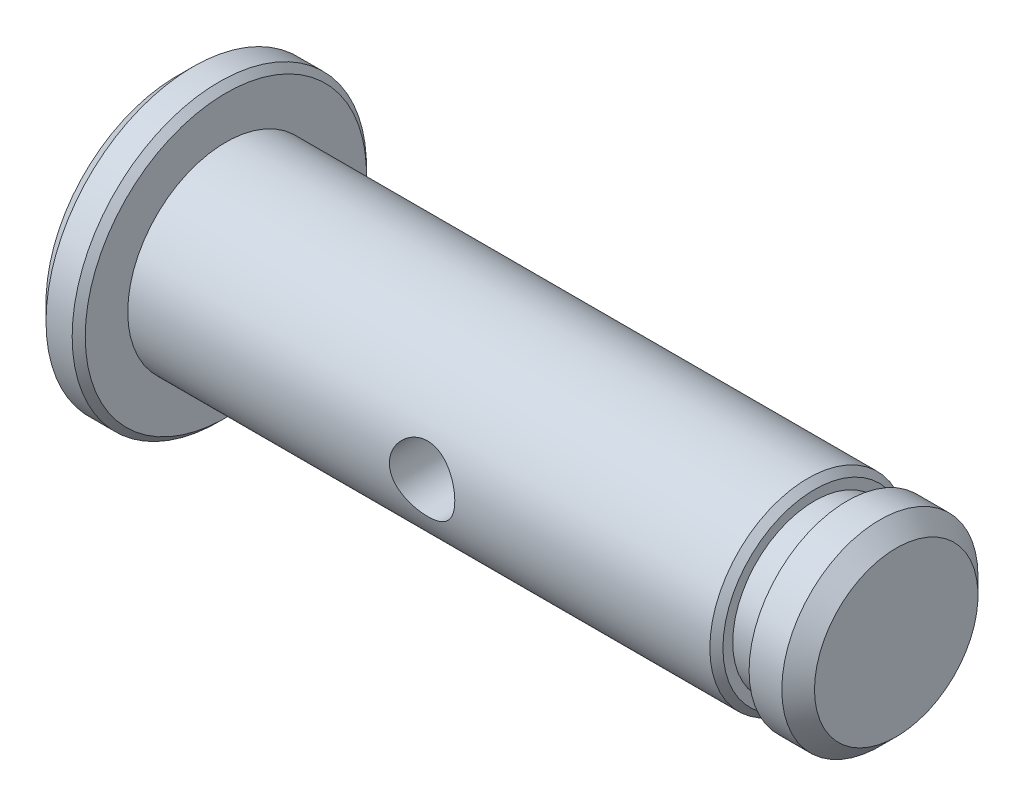
SolidWorks part; units mm, degrees
material "6061-T6 (GB)"
ref_plane "前视" through (0, 0, 0) normal (0, 0, 1) x (1, 0, 0)
ref_plane "上视" through (0, 0, 0) normal (0, 1, 0) x (1, 0, 0)
ref_plane "右视" through (0, 0, 0) normal (1, 0, 0) x (0, 0, -1)
sketch "草图1" plane through (0, 0, 0) normal (0, 0, 1) x (1, 0, 0)
  line L0 (0, 0) -> (77.1831, 0) construction
  line L1 (0, 0) -> (0, 4.5)
  line L2 (0, 4.5) -> (1.5, 4.5)
  line L3 (1.5, 4.5) -> (1.5, 3)
  line L4 (1.5, 3) -> (19.5, 3)
  line L5 (19.5, 3) -> (19.5, 2.5)
  line L6 (19.5, 2.5) -> (20.5, 2.5)
  line L7 (20.5, 2.5) -> (20.5, 3)
  line L8 (20.5, 3) -> (22, 3)
  line L9 (22, 3) -> (22, 0)
  line L10 (22, 0) -> (0, 0)
  dimension "D1" = 1.5
  dimension "D2" = 1
  dimension "D3" = 0.5
  dimension "D4" = 6
  dimension "D5" = 1.5
  dimension "D6" = 9
  dimension "D7" = 18
revolve "旋转1" add sketch "草图1" angle 360 about L0
chamfer "倒角1" distance 0.5 angle 45 2 edges at (22, 0, 3) (0, 0, 4.5)
sketch "草图2" plane through (0, 0, 0) normal (0, 0, 1) x (1, 0, 0)
  line L0 (0, 0) -> (26.5863, 0) construction
  line L1 (1.5, -4.5) -> (1.5, 4.5) construction
  circle A0 centre (10.5, 0) radius 1
  dimension "D1" = 2
  dimension "D2" = 9
extrude "切除-拉伸1" cut sketch "草图2" against normal mid plane 30
chamfer "倒角2" distance 0.2 angle 45 2 edges at (19.5, 0, 3) (1.5, 0, 4.5)
